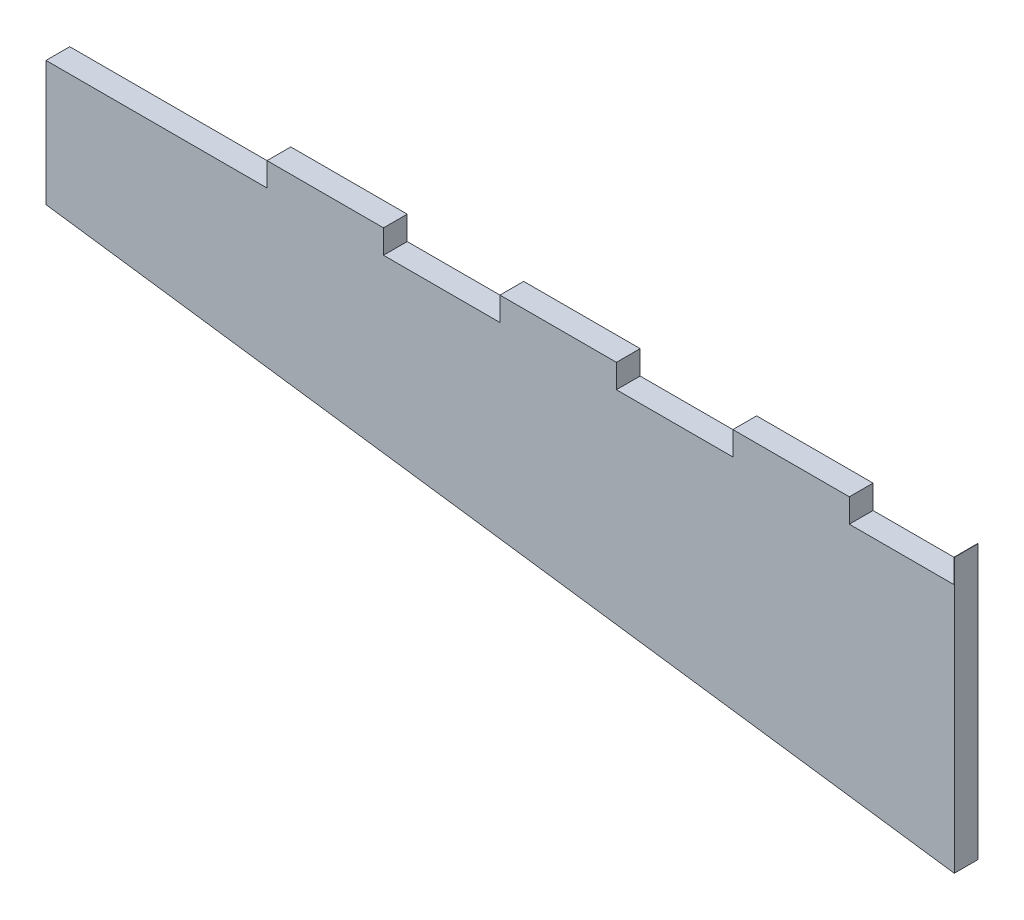
SolidWorks part; units mm, degrees
ref_plane "Front Plane" through (0, 0, 0) normal (0, 0, 1) x (1, 0, 0)
ref_plane "Top Plane" through (0, 0, 0) normal (0, 1, 0) x (1, 0, 0)
ref_plane "Right Plane" through (0, 0, 0) normal (1, 0, 0) x (0, 0, -1)
sketch "Sketch1" plane through (0, 0, 0) normal (0, 0, 1) x (1, 0, 0)
  line L1 (0, 0) -> (184.658, 0)
  line L2 (0, 0) -> (0, 30.226)
  line L3 (0, 30.226) -> (184.658, 30.226)
  line L4 (184.658, 0) -> (184.658, 30.226)
  dimension "D1" = 184.658
  dimension "D2" = 30.226
extrude "Boss-Extrude1" add sketch "Sketch1" along normal blind 4.826
sketch "Sketch2" plane through (0, 0, 0) normal (0, 0, -1) x (-1, 0, 0)
  line L0 (0, 25.4) -> (-44.9404, 25.4) construction
  line L1 (0, 25.4) -> (0, 30.226) construction
  line L2 (0, 30.226) -> (-44.9404, 30.226) construction
  line L3 (-44.9404, 30.226) -> (-44.9404, 25.4) construction
  line L4 (-68.617, 25.4) -> (-92.2937, 25.4) construction
  line L5 (-92.2937, 30.226) -> (-92.2937, 25.4) construction
  line L6 (-68.617, 30.226) -> (-68.617, 25.4) construction
  line L7 (-68.617, 30.226) -> (-92.2937, 30.226) construction
  line L8 (-115.9704, 25.4) -> (-139.6471, 25.4) construction
  line L9 (-139.6471, 30.226) -> (-139.6471, 25.4) construction
  line L10 (-115.9704, 30.226) -> (-115.9704, 25.4) construction
  line L11 (-115.9704, 30.226) -> (-139.6471, 30.226) construction
  line L12 (-163.3237, 25.4) -> (-184.5874, 25.4) construction
  line L13 (-163.3237, 30.226) -> (-163.3237, 25.4) construction
  line L14 (-184.5874, 25.4) -> (-184.5874, 30.226) construction
  line L15 (-163.3237, 30.226) -> (-184.5874, 30.226) construction
  line L16 (0, 25.4) -> (-44.9404, 25.4)
  line L17 (0, 25.4) -> (0, 30.226)
  line L18 (0, 30.226) -> (-44.9404, 30.226)
  line L19 (-44.9404, 30.226) -> (-44.9404, 25.4)
  line L20 (-68.617, 25.4) -> (-92.2937, 25.4)
  line L21 (-92.2937, 30.226) -> (-92.2937, 25.4)
  line L22 (-68.617, 30.226) -> (-68.617, 25.4)
  line L23 (-68.617, 30.226) -> (-92.2937, 30.226)
  line L24 (-115.9704, 25.4) -> (-139.6471, 25.4)
  line L25 (-139.6471, 30.226) -> (-139.6471, 25.4)
  line L26 (-115.9704, 30.226) -> (-115.9704, 25.4)
  line L27 (-115.9704, 30.226) -> (-139.6471, 30.226)
  line L28 (-163.3237, 25.4) -> (-184.5874, 25.4)
  line L29 (-163.3237, 30.226) -> (-163.3237, 25.4)
  line L30 (-184.5874, 25.4) -> (-184.5874, 30.226)
  line L31 (-163.3237, 30.226) -> (-184.5874, 30.226)
extrude "Cut-Extrude1" cut sketch "Sketch2" against normal through all
sketch "Sketch3" plane through (0, 0, 4.826) normal (0, 0, 1) x (1, 0, 0)
  line L0 (184.658, 0) -> (184.658, -25.4)
  line L1 (184.658, -25.4) -> (0, 0)
  line L2 (0, 0) -> (184.658, 0)
  dimension "D1" = 25.4
extrude "Boss-Extrude3" add sketch "Sketch3" against normal blind 4.826
equation "\"MDF\"= 0.19in"
equation "\"PVCID\" = 2.067in"
equation "\"PVCOD\" = 2.375in"
equation "\"GenDiameter\"= 60mm"
equation "\"GenCutDiameter\" = 1.8in"
equation "\"GenCutDistance\" = 1"
equation "\"TowerHeight\" = 6in"
equation "\"TowerFrontBase\" = 3in"
equation "\"FunnelHeight\" = 1in"
equation "\"FunnelAngle\" = 20"
equation "\"TowerSideBase\" = 3in"
equation "\"TowerPanelLength\" = 2in"
equation "\"TowerPanelLeeway\" = 0.5in"
equation "\"BaseLength\" = 9in"
equation "\"BaseWidth\" = 10in"
equation "\"WheelHoleLength\" = 3.25in"
equation "\"WheelHoleWidth\" = 26mm"
equation "\"WheelHoleFromBack\" = 1.5in"
equation "\"DropLength\" = 1in"
equation "\"DropWidth\" = 8.5in"
equation "\"BumperWidth\" = 2in"
equation "\"SmallHexDiameter\" = 0.185in"
equation "\"SmallHexHeight\" = 0.701in"
equation "\"ScrewSize\" = 0.106in"
equation "\"BigHexDiameter\" = 0.251in"
equation "\"BigHexHeight\" = 0.374in"
equation "\"PCBThickness\" = 0.066in"
equation "\"ConnectorHeight\" = 0.517in"
equation "\"BoardHeight\" = 0.583in"
equation "\"UnoStackHeight\" = 1.351in"
equation "\"UnoStackWidth\" = 3.053in"
equation "\"UnoStackLength\" = 3.152in"
equation "\"HBridgeWidth\" = 1.797in"
equation "\"HBridgeLength\" = 2.236in"
equation "\"DSWidth\" = 1.820in"
equation "\"DSLength\" = 1.833in"
equation "\"StepperWidth\" = 1.799in"
equation "\"StepperLength\" = 2.248in"
equation "\"ULNWidth\" = 1.304in"
equation "\"ULNLength\" = 1.545in"
equation "\"VSwitchHeight\" = 0.392in"
equation "\"VSwitchWidth\" = 0.637in"
equation "\"VSwitchLength\" = 1.097in"
equation "\"SkateWheelDiameter\" = 80mm"
equation "\"SkateWheelThickness\" = 24mm"
equation "\"BaseDistance\" = 3in"
equation "\"DummyVar\" = 2in"
equation "\"D2@Sketch1\"=\"MDF\"+1in"
equation "\"D1@Boss-Extrude1\"=\"MDF\""
equation "\"D1@Boss-Extrude3\"=\"MDF\""
